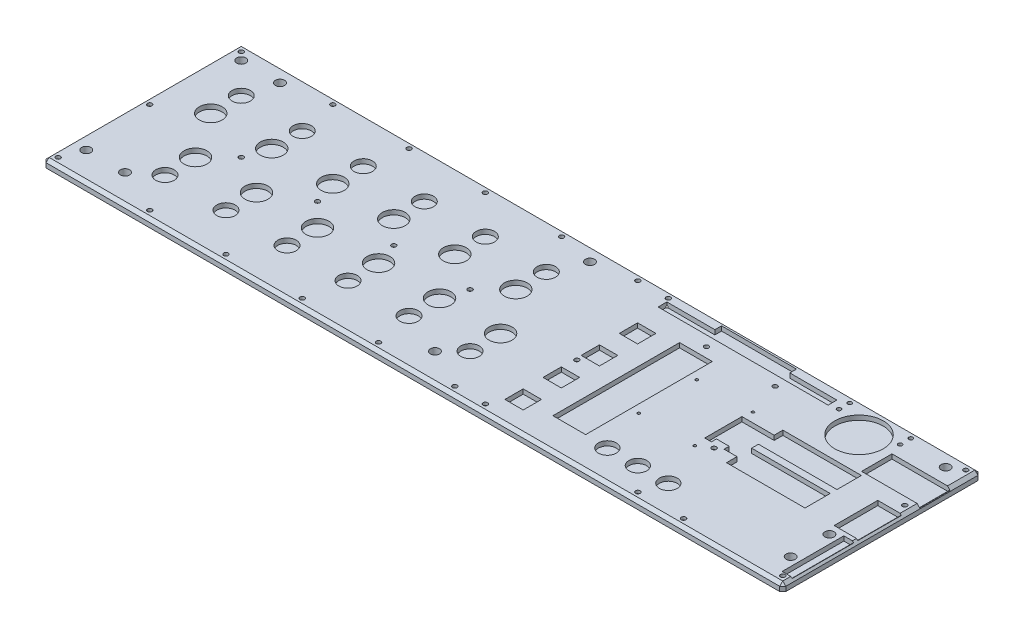
SolidWorks part; units mm, degrees
ref_plane "Front Plane" through (0, 0, 0) normal (0, 0, 1) x (1, 0, 0)
ref_plane "Top Plane" through (0, 0, 0) normal (0, 1, 0) x (1, 0, 0)
ref_plane "Right Plane" through (0, 0, 0) normal (1, 0, 0) x (0, 0, -1)
sketch "Sketch1" plane through (0, 0, 0) normal (0, 1, 0) x (1, 0, 0)
  line L1 (-180, 70) -> (305, 70)
  line L2 (-180, 70) -> (-180, -60)
  line L3 (-180, -60) -> (305, -60)
  line L4 (305, 70) -> (305, -60)
  point P4 (-180, 70)
  point P6 (305, -60)
extrude "Boss-Extrude1" add sketch "Sketch1" against normal blind 5 from offset 1.6 offset against normal yes
sketch "Sketch2" plane through (0, -1.6, 0) normal (0, 1, 0) x (1, 0, 0)
  line L0 (305, 70) -> (-180, 70) construction
  line L1 (305, -60) -> (305, 70) construction
  line L2 (-180, 70) -> (-180, -60) construction
  circle A0 centre (245, 50.5) radius 15.0148 construction
  circle A1 centre (291.8, 60) radius 3
  circle A2 centre (-170, 60) radius 3
  circle A3 centre (-144.6, 60) radius 3
  circle A4 centre (58.6, 60) radius 3
  circle A5 centre (291.8, -16.2) radius 3
  circle A6 centre (291.8, -41.6) radius 3
  circle A7 centre (300, -55) radius 1.5
  circle A8 centre (-170, -41.6) radius 3
  circle A9 centre (-144.6, -41.6) radius 3
  circle A10 centre (58.6, -41.6) radius 3
  circle A11 centre (-175, 65) radius 1.5
  circle A12 centre (-115, 65) radius 1.5
  circle A13 centre (-65, 65) radius 1.5
  circle A14 centre (-15, 65) radius 1.5
  circle A15 centre (35, 65) radius 1.5
  circle A16 centre (85, 65) radius 1.5
  circle A17 centre (105, 65) radius 1.5
  circle A18 centre (300, 65) radius 1.5
  circle A19 centre (85, -55) radius 1.5
  circle A20 centre (105, -55) radius 1.5
  circle A21 centre (205, -55) radius 1.5
  circle A22 centre (235, -55) radius 1.5
  circle A23 centre (-175, -55) radius 1.5
  circle A24 centre (-115, -55) radius 1.5
  circle A25 centre (-65, -55) radius 1.5
  circle A26 centre (-15, -55) radius 1.5
  circle A27 centre (35, -55) radius 1.5
  circle A28 centre (-175, 5) radius 1.5
  circle A29 centre (-115, 5) radius 1.5
  circle A30 centre (-65, 5) radius 1.5
  circle A31 centre (110, 0) radius 1.5
  circle A32 centre (35, 5) radius 1.5
  circle A33 centre (-15, 5) radius 1.5
  circle A34 centre (205, -5) radius 1.5
  circle A35 centre (145, 50) radius 1.5
  circle A36 centre (190, 50) radius 1.5
  circle A37 centre (300, 25) radius 1.5
  circle A38 centre (160.54, 28.1) radius 0.879
  circle A39 centre (197.37, 28.1) radius 0.879
  circle A40 centre (197.37, -10) radius 0.879
  circle A41 centre (160.54, -10) radius 0.879
  dimension "D3" = 3
  dimension "D1" = 19.5
  dimension "D2" = 60
  dimension "D4" = 20
  dimension "D5" = 265
extrude "Cut-Extrude1" cut sketch "Sketch2" against normal through all
sketch "Sketch3" plane through (0, -1.6, 0) normal (0, 1, 0) x (1, 0, 0)
  line L0 (305, 70) -> (-180, 70) construction
  line L1 (305, -60) -> (305, 70) construction
  line L2 (208.9224, -2.3883) -> (217.3882, -2.3883)
  line L3 (266.5908, 50) -> (303.9819, 50)
  line L4 (266.5908, 50) -> (266.5908, 30.0739)
  line L5 (266.5908, 30.0739) -> (303.9819, 30.0739)
  line L6 (303.9819, 50) -> (303.9819, 30.0739)
  line L7 (288.3592, 18.9249) -> (303.1307, 18.9249)
  line L8 (288.3592, 18.9249) -> (288.3592, -9.6619)
  line L9 (288.3592, -9.6619) -> (303.1307, -9.6619)
  line L10 (303.1307, 18.9249) -> (303.1307, -9.6619)
  line L11 (297.3726, -12.3054) -> (303.1307, -12.3054)
  line L12 (297.3726, -12.3054) -> (297.3726, -52.7789)
  line L13 (297.3726, -52.7789) -> (303.1307, -52.7789)
  line L14 (303.1307, -12.3054) -> (303.1307, -52.7789)
  line L15 (217.3882, 27.6953) -> (268.8536, 27.6953)
  line L16 (217.3882, 27.6953) -> (217.3882, 21.977)
  line L17 (217.3882, 11.7004) -> (268.8536, 11.7004)
  line L18 (268.8536, 27.6953) -> (268.8536, 11.7004)
  line L19 (268.8536, 7.2252) -> (217.3882, 7.2252)
  line L20 (268.8536, 7.2252) -> (268.8536, -9.267)
  line L21 (268.8536, -9.267) -> (217.3882, -9.267)
  line L22 (217.3882, -2.3883) -> (217.3882, -9.267)
  line L23 (196.255, 21.977) -> (217.3882, 21.977)
  line L24 (196.255, 21.977) -> (196.255, -2.3883)
  line L25 (196.255, -2.3883) -> (200.5925, -2.3883)
  line L26 (217.3882, 11.7004) -> (217.3882, 7.2252)
  line L27 (108.8347, 41) -> (120.8347, 41)
  line L28 (108.8347, 41) -> (108.8347, 29)
  line L29 (108.8347, 29) -> (120.8347, 29)
  line L30 (120.8347, 41) -> (120.8347, 29)
  line L35 (133.8233, 43.5526) -> (139.6368, 43.5526)
  line L36 (133.8233, 43.5526) -> (133.8233, -39.498)
  line L37 (133.8233, -39.498) -> (139.6368, -39.498)
  line L39 (149.7413, 43.5526) -> (155.278, 43.5526)
  line L41 (149.7413, -39.498) -> (155.278, -39.498)
  line L42 (155.278, 43.5526) -> (155.278, -39.498)
  line L43 (106.5809, 62.4515) -> (138.0479, 62.4515)
  line L44 (106.5809, 62.4515) -> (106.5809, 56.7168)
  line L45 (106.5809, 56.7168) -> (218.015, 56.7168)
  line L46 (218.015, 62.4515) -> (218.015, 56.7168)
  line L47 (108.8347, 16) -> (120.8347, 16)
  line L48 (108.8347, 16) -> (108.8347, 4)
  line L49 (108.8347, 4) -> (120.8347, 4)
  line L50 (120.8347, 16) -> (120.8347, 4)
  line L51 (108.8347, -9) -> (120.8347, -9)
  line L52 (108.8347, -9) -> (108.8347, -21)
  line L53 (108.8347, -21) -> (120.8347, -21)
  line L54 (120.8347, -9) -> (120.8347, -21)
  line L55 (108.8347, -34) -> (120.8347, -34)
  line L56 (108.8347, -34) -> (108.8347, -46)
  line L57 (108.8347, -46) -> (120.8347, -46)
  line L58 (120.8347, -34) -> (120.8347, -46)
  line L60 (200.5925, -2.3883) -> (200.5925, 0.933)
  line L61 (200.5925, 0.933) -> (208.9224, 0.933)
  line L62 (208.9224, -2.3883) -> (208.9224, 0.933)
  line L63 (187.1845, 62.4515) -> (218.015, 62.4515)
  line L65 (138.0479, 62.4515) -> (138.0479, 66.8297)
  line L66 (138.0479, 66.8297) -> (187.1845, 66.8297)
  line L67 (187.1845, 62.4515) -> (187.1845, 66.8297)
  line L69 (139.6368, 43.5526) -> (149.7413, 43.5526)
  line L71 (139.6368, -39.498) -> (149.7413, -39.498)
  circle A0 centre (245, 50) radius 15.9002
  circle A1 centre (223.9, 65) radius 1.3177
  circle A2 centre (223.9, 58) radius 1.3177
  circle A3 centre (264, 65) radius 1.3177
  circle A4 centre (264, 58) radius 1.3177
  circle A5 centre (170, -40) radius 5.8588
  circle A6 centre (190, -40) radius 5.8588
  circle A7 centre (210, -40) radius 5.8588
  circle A8 centre (-150, 40) radius 6.0322
  circle A9 centre (-110, 40) radius 6.0322
  circle A10 centre (-70, 40) radius 6.0322
  circle A11 centre (-30, 40) radius 6.0322
  circle A12 centre (10, 40) radius 6.0322
  circle A13 centre (50, 40) radius 6.0322
  circle A14 centre (-130, -30) radius 6.0322
  circle A15 centre (-90, -30) radius 6.0322
  circle A16 centre (-50, -30) radius 6.0322
  circle A17 centre (-10, -30) radius 6.0322
  circle A18 centre (30, -30) radius 6.0322
  circle A19 centre (70, -30) radius 6.0322
  circle A20 centre (-150, 20) radius 7.5246
  circle A21 centre (-70, 20) radius 7.5246
  circle A22 centre (-110, 20) radius 7.5246
  circle A23 centre (-30, 20) radius 7.5246
  circle A24 centre (10, 20) radius 7.5246
  circle A25 centre (50, 20) radius 7.5246
  circle A26 centre (30, -10) radius 7.5246
  circle A27 centre (70, -10) radius 7.5246
  circle A28 centre (-50, -10) radius 7.5246
  circle A29 centre (-10, -10) radius 7.5246
  circle A30 centre (-130, -10) radius 7.5246
  circle A31 centre (-90, -10) radius 7.5246
  dimension "D1" = 20
  dimension "D2" = 60
  dimension "D3" = 12
  dimension "D4" = 25
  dimension "D5" = 25
  dimension "D6" = 25
  dimension "D7" = 29
extrude "Cut-Extrude2" cut sketch "Sketch3" against normal blind 3
chamfer "Chamfer1" distance 2 angle 45 8 edges at (-180, -4.1, -70) (305, -4.1, -70) (305, -4.1, 60) (-180, -4.1, 60) (-180, -1.6, -5) (62.5, -1.6, 60) (62.5, -1.6, -70) (305, -1.6, -5)
chamfer "Chamfer2" distance 1 angle 79 3 edges at (303.1307, -1.7307, -4.6315) (303.9819, -2.5819, -40.037) (303.1307, -1.7307, 32.5421) first distance on face at (303.4054, -2.0054, -4.2816)
sketch "Sketch4" plane through (0, -6.6, 0) normal (0, -1, 0) x (1, 0, 0)
  circle A0 centre (-175, 55) radius 3.5
  circle A1 centre (-115, 55) radius 3.5
  circle A2 centre (-175, -5) radius 3.5
  circle A3 centre (-115, -5) radius 3.5
  circle A4 centre (-115, -65) radius 3.5
  circle A5 centre (-175, -65) radius 3.5
  circle A6 centre (-65, 55) radius 3.5
  circle A7 centre (-15, 55) radius 3.5
  circle A8 centre (35, 55) radius 3.5
  circle A9 centre (85, 55) radius 3.5
  circle A10 centre (105, 55) radius 3.5
  circle A11 centre (-65, -5) radius 3.5
  circle A12 centre (-15, -5) radius 3.5
  circle A13 centre (35, -5) radius 3.5
  circle A14 centre (35, -65) radius 3.5
  circle A15 centre (-15, -65) radius 3.5
  circle A16 centre (-65, -65) radius 3.5
  circle A17 centre (85, -65) radius 3.5
  circle A18 centre (105, -65) radius 3.5
  circle A19 centre (110, 0) radius 3.5
  circle A20 centre (145, -50) radius 3.5
  circle A21 centre (190, -50) radius 3.5
  circle A22 centre (300, -65) radius 3.5
  circle A23 centre (300, 55) radius 3.5
  circle A24 centre (300, -25) radius 3.5
  circle A25 centre (205, 5) radius 3.5
  circle A26 centre (205, 55) radius 3.5
  circle A27 centre (235, 55) radius 3.5
  circle A28 centre (197.37, 10) radius 3.5
  circle A29 centre (160.54, 10) radius 3.5
  circle A30 centre (160.54, -28.1) radius 3.5
  circle A31 centre (197.37, -28.1) radius 3.5
  dimension "D1" = 7
extrude "Cut-Extrude3" cut sketch "Sketch4" against normal blind 3
